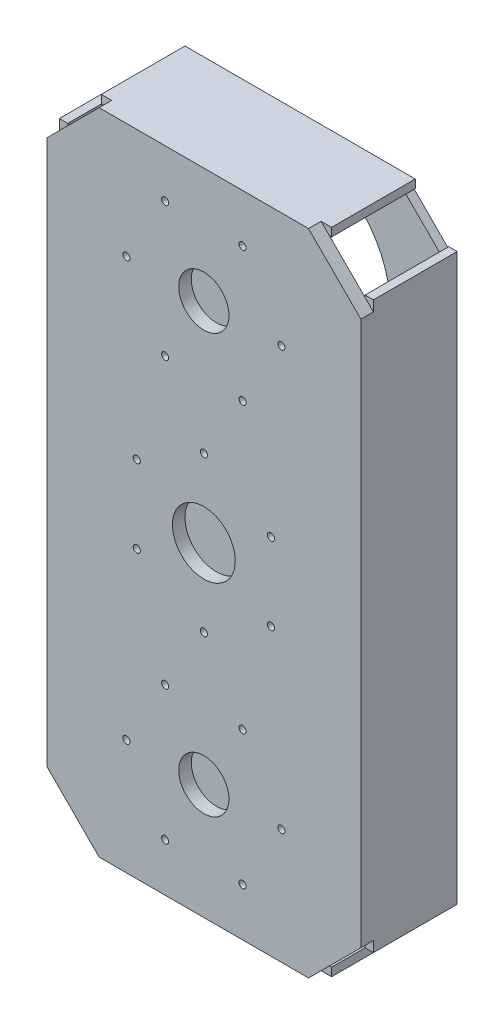
SolidWorks part; units mm, degrees
ref_plane "Front Plane" through (0, 0, 0) normal (0, 0, 1) x (1, 0, 0)
ref_plane "Top Plane" through (0, 0, 0) normal (0, 1, 0) x (1, 0, 0)
ref_plane "Right Plane" through (0, 0, 0) normal (1, 0, 0) x (0, 0, -1)
ref_plane "PL_Top_Plate_base" through (0, 0, 131) normal (0, 0, 1) x (1, 0, 0)
sketch "SK_Top_Plate" plane through (0, 0, 131) normal (0, 0, 1) x (1, 0, 0)
  line L0 (-50, -155) -> (50, -155)
  line L1 (50, -155) -> (75, -130)
  line L2 (75, -130) -> (75, 130)
  line L3 (75, 130) -> (50, 155)
  line L4 (50, 155) -> (-50, 155)
  line L5 (-50, 155) -> (-75, 130)
  line L6 (-75, 130) -> (-75, -130)
  line L7 (-75, -130) -> (-50, -155)
  circle A0 centre (37, 100) radius 1.7
  circle A1 centre (18.5, 132.0429) radius 1.7
  circle A2 centre (-18.5, 132.0429) radius 1.7
  circle A3 centre (-37, 100) radius 1.7
  circle A4 centre (-18.5, 67.9571) radius 1.7
  circle A5 centre (18.5, 67.9571) radius 1.7
  circle A6 centre (0, 100) radius 12
  circle A7 centre (37, -100) radius 1.7
  circle A8 centre (18.5, -67.9571) radius 1.7
  circle A9 centre (-18.5, -67.9571) radius 1.7
  circle A10 centre (-37, -100) radius 1.7
  circle A11 centre (-18.5, -132.0429) radius 1.7
  circle A12 centre (18.5, -132.0429) radius 1.7
  circle A13 centre (0, -100) radius 12
  circle A14 centre (32.0429, 18.5) radius 1.7
  circle A15 centre (0, 37) radius 1.7
  circle A16 centre (-32.0429, 18.5) radius 1.7
  circle A17 centre (-32.0429, -18.5) radius 1.7
  circle A18 centre (0, -37) radius 1.7
  circle A19 centre (32.0429, -18.5) radius 1.7
  circle A20 centre (0, 0) radius 15
  dimension "D17_SK_Top_Plate" = 3.4
  dimension "D20_SK_Top_Plate" = 3.4
  dimension "D23_SK_Top_Plate" = 3.4
  dimension "D26_SK_Top_Plate" = 3.4
  dimension "D29_SK_Top_Plate" = 3.4
  dimension "D32_SK_Top_Plate" = 3.4
  dimension "D35_SK_Top_Plate" = 24
  dimension "D37_SK_Top_Plate" = 3.4
  dimension "D40_SK_Top_Plate" = 3.4
  dimension "D43_SK_Top_Plate" = 3.4
  dimension "D46_SK_Top_Plate" = 3.4
  dimension "D49_SK_Top_Plate" = 3.4
  dimension "D52_SK_Top_Plate" = 3.4
  dimension "D55_SK_Top_Plate" = 24
  dimension "D57_SK_Top_Plate" = 3.4
  dimension "D60_SK_Top_Plate" = 3.4
  dimension "D62_SK_Top_Plate" = 3.4
  dimension "D65_SK_Top_Plate" = 3.4
  dimension "D68_SK_Top_Plate" = 3.4
  dimension "D70_SK_Top_Plate" = 3.4
  dimension "D73_SK_Top_Plate" = 30
  dimension "P1" = 50
  dimension "P2" = 155
  dimension "P3" = 50
  dimension "P4" = 155
  dimension "P5" = 75
  dimension "P6" = 130
  dimension "P7" = 75
  dimension "P8" = 130
  dimension "P9" = 50
  dimension "P10" = 155
  dimension "P11" = 50
  dimension "P12" = 155
  dimension "P13" = 75
  dimension "P14" = 130
  dimension "P15" = 75
  dimension "P16" = 130
  dimension "P18" = 37
  dimension "P19" = 100
  dimension "P21" = 18.5
  dimension "P22" = 132.0429
  dimension "P24" = 18.5
  dimension "P25" = 132.0429
  dimension "P27" = 37
  dimension "P28" = 100
  dimension "P30" = 18.5
  dimension "P31" = 67.9571
  dimension "P33" = 18.5
  dimension "P34" = 67.9571
  dimension "P36" = 100
  dimension "P38" = 37
  dimension "P39" = 100
  dimension "P41" = 18.5
  dimension "P42" = 67.9571
  dimension "P44" = 18.5
  dimension "P45" = 67.9571
  dimension "P47" = 37
  dimension "P48" = 100
  dimension "P50" = 18.5
  dimension "P51" = 132.0429
  dimension "P53" = 18.5
  dimension "P54" = 132.0429
  dimension "P56" = 100
  dimension "P58" = 32.0429
  dimension "P59" = 18.5
  dimension "P61" = 37
  dimension "P63" = 32.0429
  dimension "P64" = 18.5
  dimension "P66" = 32.0429
  dimension "P67" = 18.5
  dimension "P69" = 37
  dimension "P71" = 32.0429
  dimension "P72" = 18.5
extrude "Top_Plate" add sketch "SK_Top_Plate" along normal blind 6
ref_plane "PL_Front_Wall_base" through (71, 0, 0) normal (1, 0, 0) x (0, 0, -1)
sketch "SK_Front_Wall" plane through (71, 0, 0) normal (1, 0, 0) x (0, 0, -1)
  line L0 (-91, -135) -> (-91, 135)
  line L1 (-91, 135) -> (-131, 135)
  line L2 (-131, 135) -> (-131, -135)
  line L3 (-131, -135) -> (-91, -135)
  dimension "P1" = 91
  dimension "P2" = 135
  dimension "P3" = 91
  dimension "P4" = 135
  dimension "P5" = 131
  dimension "P6" = 135
  dimension "P7" = 131
  dimension "P8" = 135
extrude "Front_Wall" add sketch "SK_Front_Wall" along normal blind 4
ref_plane "PL_Back_Wall_base" through (-75, 0, 0) normal (1, 0, 0) x (0, 0, -1)
sketch "SK_Back_Wall" plane through (-75, 0, 0) normal (1, 0, 0) x (0, 0, -1)
  line L0 (-91, -135) -> (-91, 135)
  line L1 (-91, 135) -> (-131, 135)
  line L2 (-131, 135) -> (-131, -135)
  line L3 (-131, -135) -> (-91, -135)
  dimension "P1" = 91
  dimension "P2" = 135
  dimension "P3" = 91
  dimension "P4" = 135
  dimension "P5" = 131
  dimension "P6" = 135
  dimension "P7" = 131
  dimension "P8" = 135
extrude "Back_Wall" add sketch "SK_Back_Wall" along normal blind 4
ref_plane "PL_Left_Wall_base" through (0, 151, 0) normal (0, 1, 0) x (1, 0, 0)
sketch "SK_Left_Wall" plane through (0, 151, 0) normal (0, 1, 0) x (1, 0, 0)
  line L0 (-55, -91) -> (55, -91)
  line L1 (55, -91) -> (55, -131)
  line L2 (55, -131) -> (-55, -131)
  line L3 (-55, -131) -> (-55, -91)
  dimension "P1" = 55
  dimension "P2" = 91
  dimension "P3" = 55
  dimension "P4" = 91
  dimension "P5" = 55
  dimension "P6" = 131
  dimension "P7" = 55
  dimension "P8" = 131
extrude "Left_Wall" add sketch "SK_Left_Wall" along normal blind 4
ref_plane "PL_Right_Wall_base" through (0, -155, 0) normal (0, 1, 0) x (1, 0, 0)
sketch "SK_Right_Wall" plane through (0, -155, 0) normal (0, 1, 0) x (1, 0, 0)
  line L0 (-55, -91) -> (55, -91)
  line L1 (55, -91) -> (55, -131)
  line L2 (55, -131) -> (-55, -131)
  line L3 (-55, -131) -> (-55, -91)
  dimension "P1" = 55
  dimension "P2" = 91
  dimension "P3" = 55
  dimension "P4" = 91
  dimension "P5" = 55
  dimension "P6" = 131
  dimension "P7" = 55
  dimension "P8" = 131
extrude "Right_Wall" add sketch "SK_Right_Wall" along normal blind 4
ref_plane "PL_Bottom_Plate_base" through (0, 0, 91) normal (0, 0, 1) x (1, 0, 0)
sketch "SK_Bottom_Plate" plane through (0, 0, 91) normal (0, 0, 1) x (1, 0, 0)
  line L0 (-50, -155) -> (50, -155)
  line L1 (50, -155) -> (75, -130)
  line L2 (75, -130) -> (75, 130)
  line L3 (75, 130) -> (50, 155)
  line L4 (50, 155) -> (-50, 155)
  line L5 (-50, 155) -> (-75, 130)
  line L6 (-75, 130) -> (-75, -130)
  line L7 (-75, -130) -> (-50, -155)
  circle A0 centre (0, 100) radius 47
  circle A1 centre (0, -100) radius 47
  circle A2 centre (0, 0) radius 20
  dimension "D17_SK_Bottom_Plate" = 94
  dimension "D19_SK_Bottom_Plate" = 94
  dimension "D21_SK_Bottom_Plate" = 40
  dimension "P1" = 50
  dimension "P2" = 155
  dimension "P3" = 50
  dimension "P4" = 155
  dimension "P5" = 75
  dimension "P6" = 130
  dimension "P7" = 75
  dimension "P8" = 130
  dimension "P9" = 50
  dimension "P10" = 155
  dimension "P11" = 50
  dimension "P12" = 155
  dimension "P13" = 75
  dimension "P14" = 130
  dimension "P15" = 75
  dimension "P16" = 130
  dimension "P18" = 100
  dimension "P20" = 100
extrude "Bottom_Plate" add sketch "SK_Bottom_Plate" along normal blind 4
equation "\"Hip_spacing\" = 200"
equation "\"Pelvis_half_width\" = 155"
equation "\"Pelvis_half_depth\" = 75"
